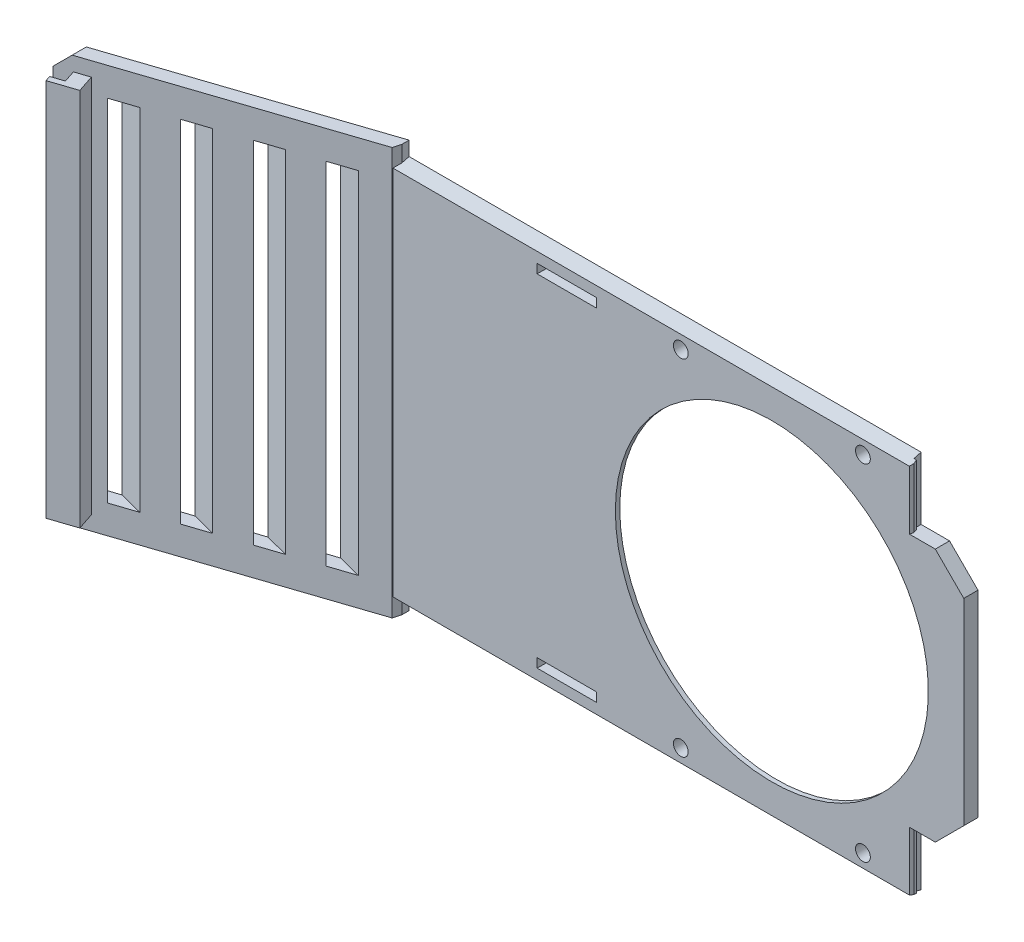
SolidWorks part; units mm, degrees
ref_plane "Front Plane" through (0, 0, 0) normal (0, 0, 1) x (1, 0, 0)
ref_plane "Top Plane" through (0, 0, 0) normal (0, 1, 0) x (1, 0, 0)
ref_plane "Right Plane" through (0, 0, 0) normal (1, 0, 0) x (0, 0, -1)
sketch "Sketch3" plane through (0, 0, 0) normal (0, 1, 0) x (1, 0, 0)
  line L0 (0, 0) -> (57.1961, 19.0654)
  line L1 (57.1961, 19.0654) -> (171.45, 19.0654)
  line L2 (171.45, 19.0654) -> (171.45, 15.8904)
  line L3 (171.45, 15.8904) -> (57.15, 15.8904)
  line L4 (57.15, 15.8904) -> (0, -3.1596)
  line L5 (0, -3.1596) -> (0, 0)
  dimension "D1" = 114.3
  dimension "D2" = 3.175
  dimension "D3" = 19.05
  dimension "D4" = 57.15
extrude "Boss-Extrude1" add sketch "Sketch3" along normal blind 84.582
sketch "Sketch4" plane through (0, 84.582, 0) normal (0, 1, 0) x (1, 0, 0)
  line L0 (57.1961, 19.0654) -> (57.1961, 15.9057)
  line L1 (57.1961, 15.9057) -> (0, -3.1596)
  line L2 (0, -3.1596) -> (0, 0)
  line L3 (0, 0) -> (57.1961, 19.0654)
extrude "Boss-Extrude2" add sketch "Sketch4" along normal blind 3.175
sketch "Sketch5" plane through (0, 0, 0) normal (0, -1, 0) x (-1, 0, 0)
  line L0 (-57.1961, 19.0654) -> (-57.1961, 15.9057)
  line L1 (-57.1961, 15.9057) -> (0, -3.1596)
  line L2 (0, -3.1596) -> (0, 0)
  line L3 (0, 0) -> (-57.1961, 19.0654)
extrude "Boss-Extrude3" add sketch "Sketch5" along normal blind 3.175
sketch "Sketch6" plane through (0.9479, 0, 2.8437) normal (0.3162, 0, 0.9487) x (0.9487, 0, -0.3162)
  line L0 (59.2908, -3.175) -> (-0.9992, -3.175) construction
  line L1 (2.5568, 84.582) -> (5.7318, 84.582)
  line L2 (2.5568, 84.582) -> (2.5568, 0)
  line L3 (2.5568, 0) -> (5.7318, 0)
  line L4 (5.7318, 84.582) -> (5.7318, 0)
  line L5 (-0.9992, 87.757) -> (59.2908, 87.757) construction
  line L6 (-0.9992, 87.757) -> (-0.9992, -3.175) construction
  dimension "D1" = 84.582
  dimension "D2" = 3.175
  dimension "D3" = 3.175
  dimension "D4" = 3.556
  dimension "D5" = 3.175
extrude "Boss-Extrude4" add sketch "Sketch6" along normal blind 4.064
sketch "Sketch7" plane through (2.4256, 0, -0.8085) normal (-0.9487, 0, 0.3162) x (0.3162, 0, 0.9487)
  line L0 (7.0615, 0) -> (2.9975, 0) construction
  line L1 (7.0615, 84.582) -> (5.7915, 84.582)
  line L2 (7.0615, 84.582) -> (7.0615, 0)
  line L3 (7.0615, 0) -> (5.7915, 0)
  line L4 (5.7915, 84.582) -> (5.7915, 0)
  dimension "D1" = 1.27
extrude "Boss-Extrude5" add sketch "Sketch7" along normal blind 2.794
sketch "Sketch8" plane through (0, 0, 0) normal (-0.3162, 0, -0.9487) x (-0.9487, 0, 0.3162)
  line L0 (0, -3.175) -> (-60.29, -3.175) construction
  line L1 (-47.948, 3.175) -> (-47.44, 3.175)
  line L2 (-47.948, 3.175) -> (-47.948, 81.407)
  line L3 (-47.948, 81.407) -> (-47.44, 81.407)
  line L4 (-47.44, 3.175) -> (-47.44, 81.407)
  line L5 (-35.098, 3.175) -> (-34.59, 3.175)
  line L6 (-35.098, 3.175) -> (-35.098, 81.407)
  line L7 (-35.098, 81.407) -> (-34.59, 81.407)
  line L8 (-34.59, 3.175) -> (-34.59, 81.407)
  line L9 (-22.248, 3.175) -> (-21.74, 3.175)
  line L10 (-22.248, 3.175) -> (-22.248, 81.407)
  line L11 (-22.248, 81.407) -> (-21.74, 81.407)
  line L12 (-21.74, 3.175) -> (-21.74, 81.407)
  line L13 (-9.398, 3.175) -> (-8.89, 3.175)
  line L14 (-9.398, 3.175) -> (-9.398, 81.407)
  line L15 (-9.398, 81.407) -> (-8.89, 81.407)
  line L16 (-8.89, 3.175) -> (-8.89, 81.407)
  line L17 (-60.29, 87.757) -> (0, 87.757) construction
  line L18 (0, 87.757) -> (0, -3.175) construction
  line L19 (-9.398, 81.407) -> (-21.74, 81.407) construction
  line L20 (-22.248, 81.407) -> (-34.59, 81.407) construction
  line L21 (-35.098, 81.407) -> (-47.44, 81.407) construction
  line L22 (-47.948, 81.407) -> (-60.29, 81.407) construction
  line L23 (-60.29, 84.582) -> (-60.29, 0) construction
  dimension "D1" = 6.35
  dimension "D2" = 6.35
  dimension "D3" = 6.35
  dimension "D4" = 6.35
  dimension "D5" = 6.35
  dimension "D6" = 0.508
  dimension "D7" = 8.89
extrude "Cut-Extrude1" cut sketch "Sketch8" against normal through all
chamfer "Chamfer1" distance 3.175 angle 57 4 edges at (45.0055, 42.291, -15.0018) (32.8149, 42.291, -10.9383) (20.6244, 42.291, -6.8748) (8.4338, 42.291, -2.8113)
chamfer "Chamfer2" distance 3.175 angle 57 4 edges at (46.4353, 42.291, -12.3188) (34.2448, 42.291, -8.2553) (22.0542, 42.291, -4.1918) (9.8636, 42.291, -0.1282)
sketch "Sketch10" plane through (0, 0, -19.0654) normal (0, 0, -1) x (-1, 0, 0)
  line L0 (-171.45, 84.582) -> (-171.45, 0) construction
  line L1 (-141.3256, 42.291) -> (-141.3256, 84.582) construction
  line L2 (-171.45, 84.582) -> (-57.1961, 84.582) construction
  line L3 (-141.3256, 42.291) -> (-141.3256, 0) construction
  line L4 (-171.45, 0) -> (-57.1961, 0) construction
  circle A0 centre (-141.3256, 42.291) radius 38.1 construction
  circle A1 centre (-141.3256, 42.291) radius 34.925
  circle A2 centre (-161.6456, 80.772) radius 1.651
  circle A3 centre (-121.0056, 80.772) radius 1.651
  circle A4 centre (-121.0056, 3.81) radius 1.651
  circle A5 centre (-161.6456, 3.81) radius 1.651
  circle A6 centre (-161.6456, 3.81) radius 2.921 construction
  dimension "D2" = 76.2
  dimension "D3" = 69.85
  dimension "D4" = 3.302
  dimension "D5" = 3.302
  dimension "D6" = 3.302
  dimension "D7" = 3.302
  dimension "D16" = 5.842
  dimension "D1" = 30.1244
  dimension "D8" = 20.32
  dimension "D9" = 20.32
  dimension "D10" = 20.32
  dimension "D11" = 20.32
  dimension "D12" = 3.81
  dimension "D13" = 3.81
  dimension "D14" = 3.81
  dimension "D15" = 3.81
sketch "Sketch11" plane through (171.45, 0, 0) normal (1, 0, 0) x (0, 0, -1)
  line L0 (15.8904, 84.582) -> (15.8904, 0) construction
  line L1 (15.8904, 70.612) -> (19.0654, 70.612)
  line L2 (15.8904, 70.612) -> (15.8904, 13.97)
  line L3 (15.8904, 13.97) -> (19.0654, 13.97)
  line L4 (19.0654, 70.612) -> (19.0654, 13.97)
  line L5 (19.0654, 42.291) -> (19.0654, 0) construction
  line L6 (19.0654, 4.191) -> (19.0654, 80.391) construction
  line L7 (15.9057, 84.582) -> (19.0654, 84.582) construction
  dimension "D1" = 13.97
  dimension "D2" = 13.97
extrude "Boss-Extrude6" add sketch "Sketch11" along normal blind 12.7
chamfer "Chamfer3" distance 6.35 angle 45 2 edges at (184.15, 13.97, -17.4779) (184.15, 70.612, -17.4779)
extrude "Cut-Extrude2" cut sketch "Sketch10" against normal blind 12.7
chamfer "Chamfer4" distance 3.175 angle 45 2 edges at (0, 87.757, 1.5798) (0, -3.175, 1.5798)
chamfer "Chamfer5" distance 3.175 angle 15 2 edges at (114.3, 0, -15.8904) (114.3, 84.582, -15.8904)
chamfer "Chamfer6" distance 1.5875 angle 15 2 edges at (57.1961, -1.1642, -15.9057) (57.1961, 85.7462, -15.9057)
sketch "Sketch12" plane through (0, 0, -19.0654) normal (0, 0, -1) x (-1, 0, 0)
  line L0 (-57.1961, 84.582) -> (-57.1961, 0) construction
  line L1 (-88.9461, 81.407) -> (-102.1541, 81.407)
  line L2 (-88.9461, 81.407) -> (-88.9461, 79.375)
  line L3 (-88.9461, 79.375) -> (-102.1541, 79.375)
  line L4 (-102.1541, 81.407) -> (-102.1541, 79.375)
  line L5 (-88.9461, 5.207) -> (-102.1541, 5.207)
  line L6 (-88.9461, 5.207) -> (-88.9461, 3.175)
  line L7 (-88.9461, 3.175) -> (-102.1541, 3.175)
  line L8 (-102.1541, 5.207) -> (-102.1541, 3.175)
  line L11 (-171.45, 84.582) -> (-57.1961, 84.582) construction
  line L12 (-171.45, 0) -> (-57.1961, 0) construction
  dimension "D1" = 31.75
  dimension "D2" = 31.75
  dimension "D3" = 2.032
  dimension "D4" = 2.032
  dimension "D5" = 13.208
  dimension "D6" = 13.208
  dimension "D7" = 3.175
  dimension "D8" = 3.175
extrude "Cut-Extrude3" cut sketch "Sketch12" against normal through all
sketch "Sketch13" plane through (0, 0, -19.0654) normal (0, 0, -1) x (-1, 0, 0)
  circle A0 centre (-129.8987, 9.5282) radius 0.2267
  circle A1 centre (-141.3256, 42.291) radius 34.925 construction
  circle A2 centre (-141.3256, 42.291) radius 38.354
  dimension "D1" = 76.708
extrude "Cut-Extrude4" cut sketch "Sketch13" against normal blind 1.5875
chamfer "Chamfer8" distance 3.429 angle 10 1 edges at (106.4006, 42.291, -17.4779)
sketch "Sketch14" plane through (171.45, 0, 0) normal (1, 0, 0) x (0, 0, -1)
  line L0 (15.8904, 70.612) -> (15.8904, 83.7313)
  line L1 (15.8904, 83.7313) -> (17.4779, 84.1566)
  line L2 (19.0654, 84.582) -> (15.8904, 83.7313) construction
  line L3 (17.4779, 84.1566) -> (17.4779, 70.612)
  line L4 (19.0654, 70.612) -> (15.8904, 70.612) construction
  line L5 (17.4779, 70.612) -> (15.8904, 70.612)
  line L6 (15.8904, 13.97) -> (17.4779, 13.97)
  line L7 (15.8904, 13.97) -> (19.0654, 13.97) construction
  line L8 (17.4779, 13.97) -> (17.4779, 0.4254)
  line L9 (15.8904, 0.8507) -> (19.0654, 0) construction
  line L10 (17.4779, 0.4254) -> (15.8904, 0.8507)
  line L11 (15.8904, 0.8507) -> (15.8904, 13.97)
extrude "Boss-Extrude7" add sketch "Sketch14" along normal blind 0.762
chamfer "Chamfer9" distance 0.7937 angle 15 4 edges at (172.212, 7.1977, -17.4779) (172.212, 7.4104, -15.8904) (172.212, 77.3843, -17.4779) (172.212, 77.1716, -15.8904)
